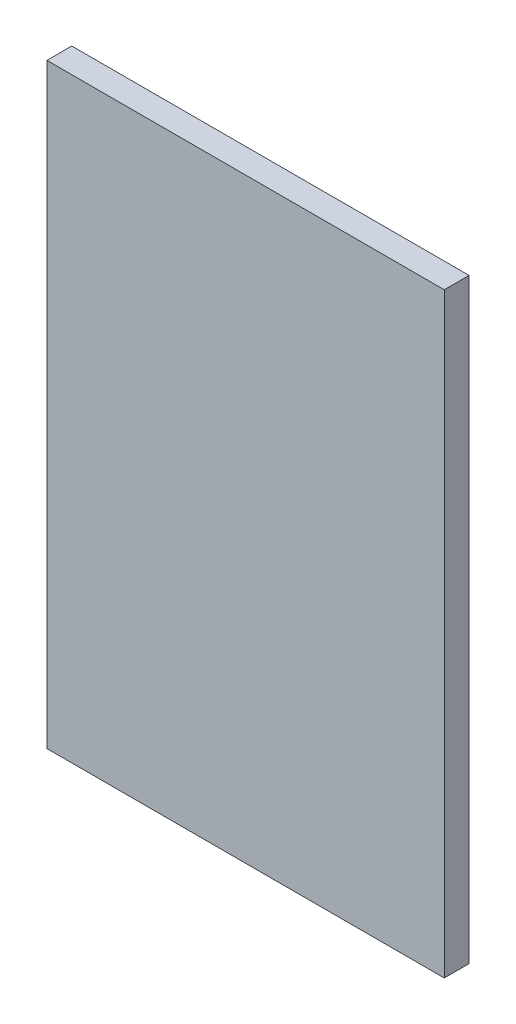
SolidWorks part; units mm, degrees
ref_plane "Front Plane" through (0, 0, 0) normal (0, 0, 1) x (1, 0, 0)
ref_plane "Top Plane" through (0, 0, 0) normal (0, 1, 0) x (1, 0, 0)
ref_plane "Right Plane" through (0, 0, 0) normal (1, 0, 0) x (0, 0, -1)
sketch "Sketch1" plane through (0, 0, 0) normal (0, 0, 1) x (1, 0, 0)
  line L1 (0, 0) -> (101.6, 0)
  line L2 (0, 0) -> (0, 152.4)
  line L3 (0, 152.4) -> (101.6, 152.4)
  line L4 (101.6, 0) -> (101.6, 152.4)
  dimension "D1" = 152.4
  dimension "D2" = 101.6
extrude "Boss-Extrude1" add sketch "Sketch1" along normal blind 6.35
